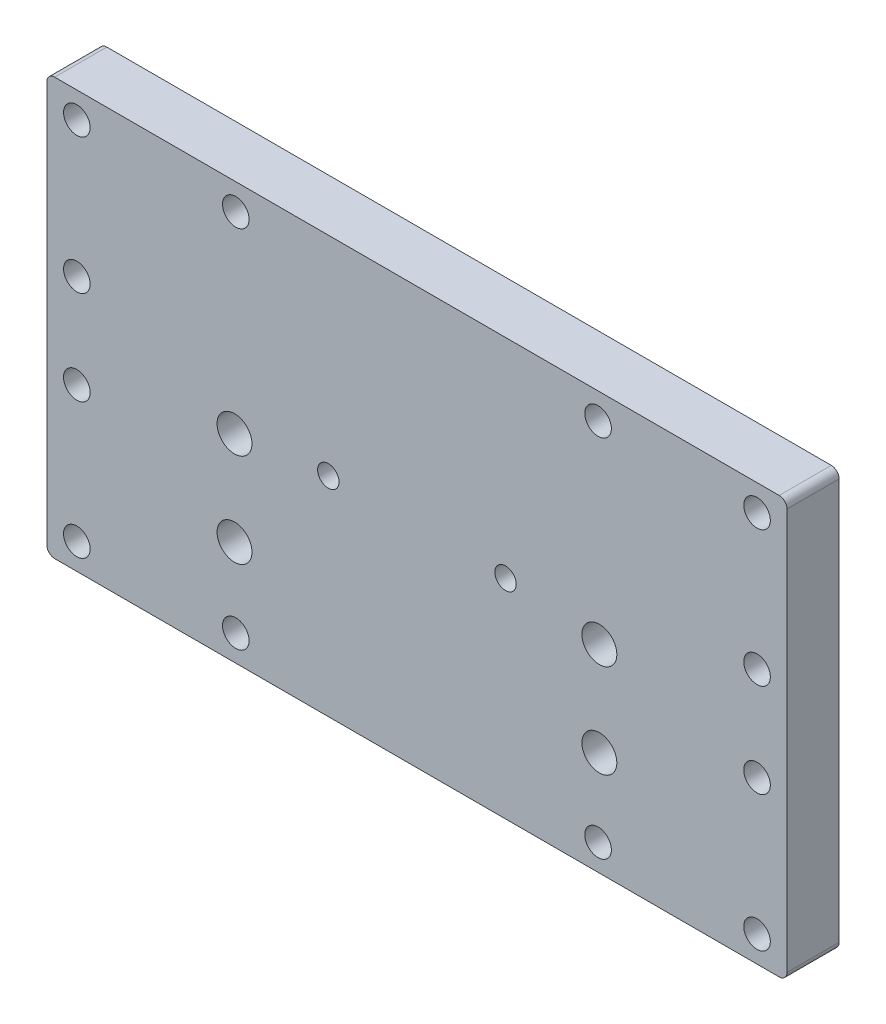
SolidWorks part; units mm, degrees
ref_plane "Front Plane" through (0, 0, 0) normal (0, 0, 1) x (1, 0, 0)
ref_plane "Top Plane" through (0, 0, 0) normal (0, 1, 0) x (1, 0, 0)
ref_plane "Right Plane" through (0, 0, 0) normal (1, 0, 0) x (0, 0, -1)
sketch "Sketch1" plane through (0, 0, 0) normal (0, 0, 1) x (1, 0, 0)
  line L1 (-71, -40) -> (71, -40)
  line L2 (-71, -40) -> (-71, 40)
  line L3 (-71, 40) -> (71, 40)
  line L4 (71, -40) -> (71, 40)
  line L5 (-71, -40) -> (71, 40) construction
  line L6 (-71, 40) -> (71, -40) construction
  point P0 (0, 0)
  dimension "D1" = 80
  dimension "D2" = 142
extrude "Boss-Extrude1" add sketch "Sketch1" along normal mid plane 10
sketch "Sketch2" plane through (0, 0, 5) normal (0, 0, 1) x (1, 0, 0)
  line L3 (-65.25, 40) -> (-65.25, -40)
  line L4 (-65.25, 40) -> (-65.25, -40) construction
  line L6 (65.25, -40) -> (65.25, 40)
  line L7 (65.25, -40) -> (65.25, 40) construction
  line L13 (-34.75, 40) -> (-34.75, -40)
  line L14 (-34.75, 40) -> (-34.75, -40) construction
  line L16 (34.75, -40) -> (34.75, 40)
  line L18 (34.75, -40) -> (34.75, 40) construction
  line L20 (71, 35) -> (-71, 35)
  line L21 (71, 35) -> (-71, 35) construction
  line L23 (-71, -35) -> (71, -35)
  line L24 (-71, -35) -> (71, -35) construction
  line L26 (71, 9) -> (-71, 9)
  line L27 (71, 9) -> (-71, 9) construction
  line L29 (-71, -9) -> (71, -9)
  line L30 (-71, -9) -> (71, -9) construction
  circle A0 centre (-65.25, 35) radius 2.55
  circle A1 centre (-34.75, 35) radius 2.55
  circle A3 centre (-65.25, 9) radius 2.55
  circle A4 centre (65.25, 35) radius 2.55
  circle A5 centre (65.25, 9) radius 2.55
  circle A7 centre (34.75, 35) radius 2.55
  circle A8 centre (-65.25, -9) radius 2.55
  circle A10 centre (-34.75, -35) radius 2.55
  circle A11 centre (-65.25, -35) radius 2.55
  circle A13 centre (65.25, -9) radius 2.55
  circle A14 centre (65.25, -35) radius 2.55
  circle A15 centre (34.75, -35) radius 2.55
  dimension "D9" = 5.1
  dimension "D11" = 5.1
  dimension "D12" = 5.1
  dimension "D13" = 5.1
  dimension "D14" = 5.1
  dimension "D15" = 5.1
  dimension "D17" = 5.1
  dimension "D18" = 5.1
  dimension "D20" = 5.1
  dimension "D21" = 5.1
  dimension "D23" = 5.1
  dimension "D24" = 5.1
  dimension "D1" = 5.75
  dimension "D2" = 5.75
  dimension "D3" = 36.25
  dimension "D4" = 36.25
  dimension "D5" = 5
  dimension "D6" = 5
  dimension "D7" = 31
  dimension "D8" = 31
extrude "Cut-Extrude1" cut sketch "Sketch2" against normal through all
sketch "Sketch3" plane through (0, 0, 5) normal (0, 0, 1) x (1, 0, 0)
  line L0 (-71, -40) -> (71, -40) construction
  line L1 (-17, 0) -> (17, 0) construction
  line L7 (0, 40) -> (0, -40) construction
  line L8 (71, 40) -> (-71, 40) construction
  circle A0 centre (-17, 0) radius 2.05
  circle A3 centre (17, 0) radius 2.05
  point P0 (0, 0)
  dimension "D3" = 4.1
  dimension "D4" = 4.1
  dimension "D5" = 17
  dimension "D2" = 34
  dimension "D1" = 40
extrude "Cut-Extrude2" cut sketch "Sketch3" against normal through all
sketch "Sketch4" plane through (0, 0, 5) normal (0, 0, 1) x (1, 0, 0)
  line L0 (0, 40) -> (0, -40) construction
  line L1 (-35, -20) -> (35, -20) construction
  line L2 (-35, -20) -> (-35, -2) construction
  line L3 (-35, -2) -> (35, -2) construction
  line L4 (35, -20) -> (35, -2) construction
  line L5 (-35, -20) -> (35, -2) construction
  line L6 (-35, -2) -> (35, -20) construction
  line L7 (71, 40) -> (-71, 40) construction
  line L8 (-71, -40) -> (71, -40) construction
  circle A0 centre (-35, -2) radius 3.35
  circle A1 centre (35, -2) radius 3.35
  circle A2 centre (35, -20) radius 3.35
  circle A3 centre (-35, -20) radius 3.35
  point P0 (0, -11)
  dimension "D3" = 6.7
  dimension "D4" = 6.7
  dimension "D5" = 6.7
  dimension "D6" = 6.7
  dimension "D1" = 70
  dimension "D2" = 18
  dimension "D7" = 20
extrude "Cut-Extrude3" cut sketch "Sketch4" against normal through all
fillet "Fillet1" radius 1.5 4 edges at (-71, -40, 0) (71, -40, 0) (71, 40, 0) (-71, 40, 0)
equation "\"D4@Sketch3\"=\"D3@Sketch3\""
equation "\"D4@Sketch4\" = \"D3@Sketch4\""
equation "\"D5@Sketch4\"=\"D3@Sketch4\""
equation "\"D6@Sketch4\"=\"D3@Sketch4\""
